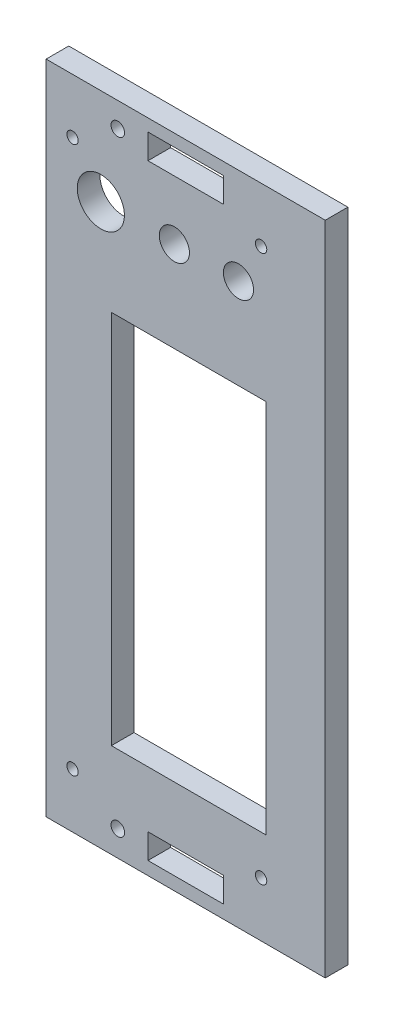
SolidWorks part; units mm, degrees
ref_plane "Plano frontal" through (0, 0, 0) normal (0, 0, 1) x (1, 0, 0)
ref_plane "Plano superior" through (0, 0, 0) normal (0, 1, 0) x (1, 0, 0)
ref_plane "Plano direito" through (0, 0, 0) normal (1, 0, 0) x (0, 0, -1)
sketch "Model" plane through (0, 0, 0) normal (0, 0, 1) x (1, 0, 0)
  line L0 (89.122, 131.8535) -> (48.122, 131.8535)
  line L1 (30.822, 181.3535) -> (30.822, 7.3536)
  line L2 (57.822, 17.4318) -> (57.822, 10.8318)
  line L3 (77.822, 17.4318) -> (57.822, 17.4318)
  line L4 (89.122, 32.3536) -> (89.122, 131.8535)
  line L5 (48.122, 131.8535) -> (48.122, 32.3536)
  line L6 (104.822, 7.3536) -> (104.822, 181.3535)
  line L7 (104.822, 181.3535) -> (30.822, 181.3535)
  line L8 (30.822, 7.3536) -> (104.822, 7.3536)
  line L9 (48.122, 32.3536) -> (89.122, 32.3536)
  line L10 (77.822, 171.5088) -> (77.822, 178.1088)
  line L11 (57.822, 171.5088) -> (77.822, 171.5088)
  line L12 (57.822, 178.1088) -> (57.822, 171.5088)
  line L13 (77.822, 178.1088) -> (57.822, 178.1088)
  line L14 (77.822, 10.8318) -> (77.822, 17.4318)
  line L15 (57.822, 10.8318) -> (77.822, 10.8318)
  circle A0 centre (87.822, 21.8536) radius 1.5
  circle A1 centre (49.822, 14.1318) radius 1.8
  circle A2 centre (37.822, 21.8536) radius 1.5
  circle A3 centre (87.822, 166.8535) radius 1.5
  circle A4 centre (81.822, 155.8535) radius 4
  circle A5 centre (64.822, 155.8535) radius 4
  circle A6 centre (45.322, 155.8535) radius 6.25
  circle A7 centre (37.822, 166.8535) radius 1.5
  circle A8 centre (49.822, 174.8088) radius 1.8
extrude "Ressalto-extrusão1" add sketch "Model" along normal blind 6
ref_axis "Eixo1" through (37.822, 166.8535, 6) along (0, 0, -1)
ref_axis "Eixo2" through (87.822, 166.8535, 6) along (0, 0, -1)
ref_axis "Eixo3" through (87.822, 21.8536, 6) along (0, 0, -1)
ref_axis "Eixo4" through (37.822, 21.8536, 6) along (0, 0, -1)
ref_plane "Plano1" through (0, 21.8536, 0) normal (0, -1, 0) x (-1, 0, 0)
ref_plane "Plano2" through (0, 166.8535, 0) normal (0, -1, 0) x (-1, 0, 0)
ref_plane "Plano3" through (0, 94.3536, 0) normal (0, -1, 0) x (-1, 0, 0)
ref_plane "Plano4" through (87.822, 0, 0) normal (-1, 0, 0) x (0, 0, 1)
ref_plane "Plano5" through (37.822, 0, 0) normal (1, 0, 0) x (0, 0, -1)
ref_plane "Plano6" through (62.822, 0, 0) normal (1, 0, 0) x (0, 0, -1)
ref_plane "Plano7" through (67.822, 0, 0) normal (1, 0, 0) x (0, 0, -1)
ref_plane "Plano8" through (0, 14.1318, 0) normal (0, 1, 0) x (1, 0, 0)
ref_plane "Plano9" through (0, 174.8088, 0) normal (0, -1, 0) x (-1, 0, 0)
